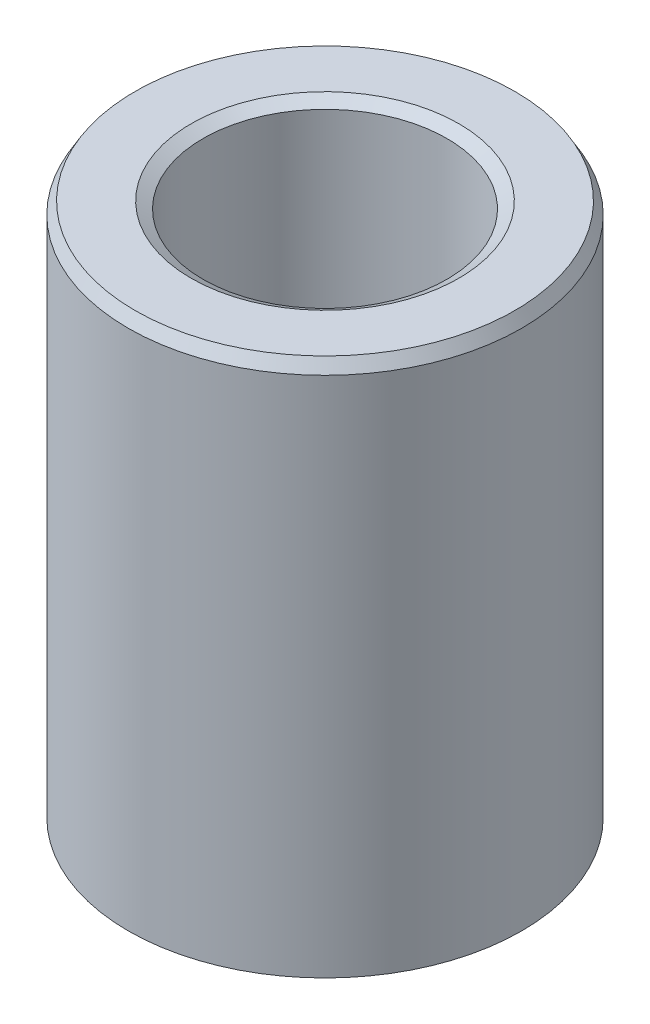
SolidWorks part; units mm, degrees
ref_plane "Front Plane" through (0, 0, 0) normal (0, 0, 1) x (1, 0, 0)
ref_plane "Top Plane" through (0, 0, 0) normal (0, 1, 0) x (1, 0, 0)
ref_plane "Right Plane" through (0, 0, 0) normal (1, 0, 0) x (0, 0, -1)
sketch "Sketch1" plane through (0, 0, 0) normal (0, 1, 0) x (1, 0, 0)
  circle A0 centre (0, 0) radius 40
  dimension "SLEEVE_OD" = 80
extrude "Boss-Extrude1" add sketch "Sketch1" along normal blind 109.9429
sketch "Sketch2" plane through (0, 0, 0) normal (0, 1, 0) x (1, 0, 0)
  circle A0 centre (0, 0) radius 24.8056
  dimension "BORE_D" = 49.6112
extrude "Cut-Extrude1" cut sketch "Sketch2" along normal through all
chamfer "Chamfer1" distance 2.4213 angle 30 4 edges at (0, 109.9429, 24.8056) (0, 0, 24.8056) (0, 0, 40) (0, 109.9429, 40) first distance on face at (0, 109.9429, 24.8056) first distance on face at (0, 0, 24.8056) first distance on face at (0, 109.9429, 40)
